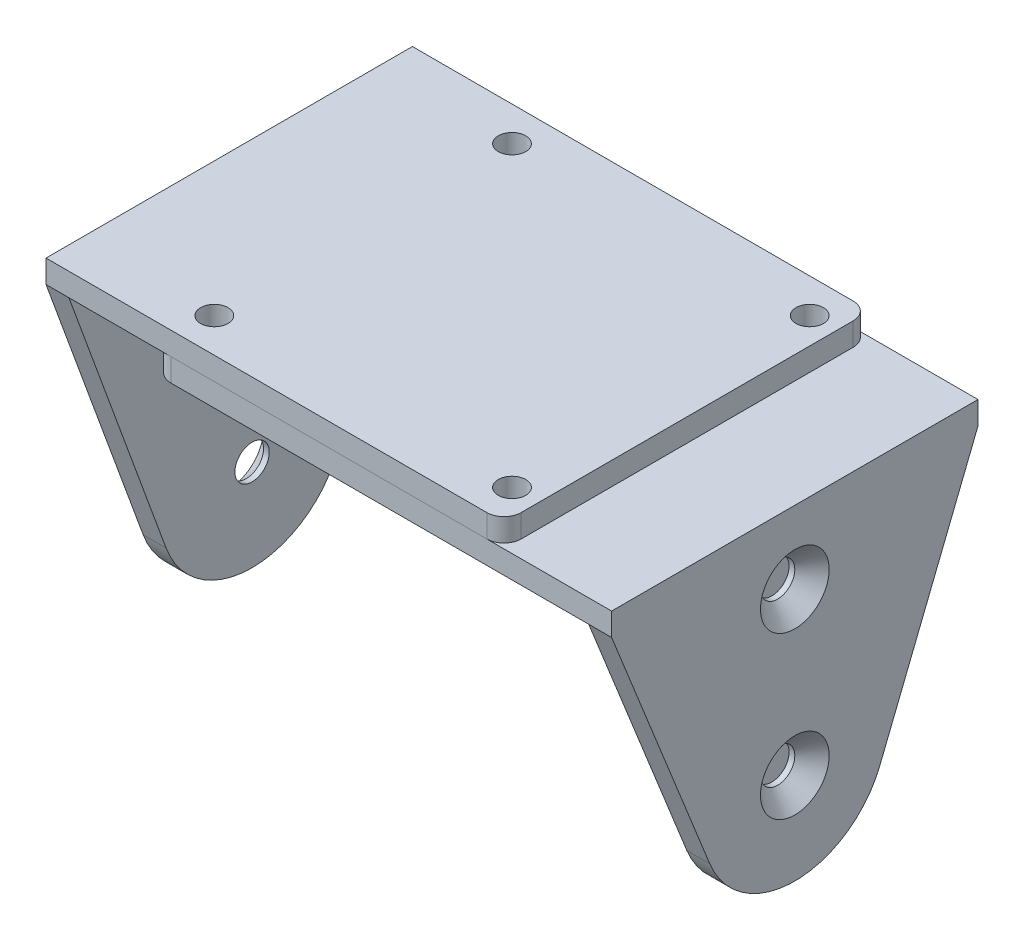
SolidWorks part; units mm, degrees
ref_plane "Спереди" through (0, 0, 0) normal (0, 0, 1) x (1, 0, 0)
ref_plane "Сверху" through (0, 0, 0) normal (0, 1, 0) x (1, 0, 0)
ref_plane "Справа" through (0, 0, 0) normal (1, 0, 0) x (0, 0, -1)
sketch "Эскиз1" plane through (0, 0, 0) normal (0, 1, 0) x (1, 0, 0)
  line L0 (0, 39.0615) -> (0, -43.4509) construction
  line L1 (-31.8334, 0) -> (63.9703, 0) construction
  line L2 (0, 16) -> (40, 16)
  line L3 (0, 16) -> (0, -16)
  line L4 (0, -16) -> (40, -16)
  line L5 (40, 16) -> (40, -16)
  line L7 (37.7, -13) -> (11.7, -13) construction
  line L8 (37.7, -13) -> (37.7, 13) construction
  line L9 (37.7, 13) -> (11.7, 13) construction
  line L10 (11.7, -13) -> (11.7, 13) construction
  line L11 (37.7, -13) -> (11.7, 13) construction
  line L12 (37.7, 13) -> (11.7, -13) construction
  circle A0 centre (11.7, 13) radius 1.2
  circle A1 centre (37.7, 13) radius 1.2
  circle A2 centre (37.7, -13) radius 1.2
  circle A3 centre (11.7, -13) radius 1.2
  point P9 (24.7, 0)
  dimension "D6" = 2.4
  dimension "D1" = 32
  dimension "D2" = 40
  dimension "D3" = 11.7
  dimension "D4" = 26
  dimension "D5" = 26
  dimension "D7" = 2
  dimension "D8" = 2
extrude "уголок 1 - основание" add sketch "Эскиз1" along normal blind 2
sketch "Эскиз2" plane through (0, 0, 0) normal (0, 1, 0) x (1, 0, 0)
  line L0 (-7.9027, 0) -> (56.365, 0) construction
  line L1 (49.4, 26.5876) -> (49.4, -26.9307) construction
  line L4 (37.7, -13) -> (11.7, -13) construction
  line L5 (37.7, -13) -> (37.7, 13) construction
  line L6 (37.7, 13) -> (11.7, 13) construction
  line L7 (11.7, -13) -> (11.7, 13) construction
  line L8 (37.7, -13) -> (11.7, 13) construction
  line L9 (37.7, 13) -> (11.7, -13) construction
  line L10 (49.4, -16) -> (9.4, -16)
  line L11 (49.4, -16) -> (49.4, 16)
  line L12 (49.4, 16) -> (9.4, 16)
  line L13 (9.4, -16) -> (9.4, 16)
  line L14 (49.4, -16) -> (9.4, 16) construction
  line L15 (49.4, 16) -> (9.4, -16) construction
  circle A0 centre (11.7, 13) radius 1.2
  circle A1 centre (37.7, 13) radius 1.2
  circle A2 centre (37.7, -13) radius 1.2
  circle A3 centre (11.7, -13) radius 1.2
  point P7 (24.7, 0)
  point P14 (29.4, 0)
  dimension "D3" = 2.4
  dimension "D4" = 2
  dimension "D1" = 11.7
  dimension "D2" = 26
  dimension "D6" = 40
  dimension "D7" = 32
  dimension "D5" = 2
extrude "уголок 2 - основание" add sketch "Эскиз2" against normal blind 2 separate body
sketch "Эскиз3" plane through (0, 0, 0) normal (-1, 0, 0) x (0, 0, 1)
  line L0 (0, 8.4121) -> (0, -39.4718) construction
  line L1 (-16, 0) -> (-7.5122, -23.179)
  line L2 (16, 0) -> (7.5122, -23.179)
  line L3 (-16, 0) -> (16, 0)
  line L5 (-16, 2) -> (16, 2) construction
  arc A0 (-7.5122, -23.179) -> (7.5122, -23.179) centre (0, -20.4282) ccw
  circle A1 centre (0, -20.4282) radius 1.5
  point P12 (-28.1067, -11.0581)
  dimension "D1" = 8
  dimension "D2" = 3
  dimension "D3" = 22.4282
extrude "уголок 1 - бок" add sketch "Эскиз3" against normal blind 2
sketch "Эскиз4" plane through (49.4, 0, 0) normal (1, 0, 0) x (0, 0, -1)
  line L0 (0, 14.6414) -> (0, -44.7384) construction
  line L1 (16, -2) -> (7.4263, -23.4031)
  line L2 (-16, -2) -> (-7.4263, -23.4031)
  line L3 (-16, 0) -> (16, 0) construction
  line L4 (-16, -2) -> (16, -2)
  circle A0 centre (0, -20.4282) radius 1.5
  arc A1 (-7.4263, -23.4031) -> (7.4263, -23.4031) centre (0, -20.4282) ccw
  circle A2 centre (0, -6.35) radius 1.5
  dimension "D1" = 3
  dimension "D2" = 8
  dimension "D3" = 3
  dimension "D4" = 6.35
extrude "уголок 2 - бок" add sketch "Эскиз4" against normal blind 2
fillet "Скругление1" radius 1.5 2 edges at (9.4, -1, 16) (9.4, -1, -16)
fillet "Скругление2" radius 1.5 2 edges at (40, 1, -16) (40, 1, 16)
chamfer "Фаска1" distance 1.5 angle 45 2 edges at (49.4, -20.4282, -1.5) (49.4, -6.35, -1.5)
chamfer "Фаска2" distance 1.5 angle 45 1 edges at (0, -20.4282, 1.5)
sketch "Эскиз5" plane through (47.4, 0, 0) normal (-1, 0, 0) x (0, 0, 1)
  line L0 (0, -35.2177) -> (0, 5.9258) construction
  line L1 (4.9, -2.3782) -> (-4.9, -2.3782)
  line L2 (4.9, -2.3782) -> (6.4256, -19.8677)
  line L3 (-4.9, -2.3782) -> (-6.4256, -19.8677)
  arc A0 (-6.4256, -19.8677) -> (6.4256, -19.8677) centre (0, -20.4282) ccw
  point P8 (0, -26.8782)
  point P9 (0, -2.3782)
  dimension "D1" = 6.45
  dimension "D2" = 24.5
  dimension "D3" = 9.8
extrude "Бобышка-Вытянуть5" add sketch "Эскиз5" along normal blind 2.6 separate body
sketch "Эскиз6" plane through (44.8, 0, 0) normal (-1, 0, 0) x (0, 0, 1)
  circle A0 centre (0, -20.4282) radius 4.85
  dimension "D1" = 9.7
extrude "Бобышка-Вытянуть6" add sketch "Эскиз6" along normal blind 1.6 separate body
chamfer "Фаска3" distance 1.4 angle 45 1 edges at (43.2, -20.4282, 4.85)
ref_axis "Ось кручения" through (56.3089, -20.4282, 0) along (-1, 0, 0)
ref_axis "Ось2" through (37.7, 4.7326, -13) along (0, -1, 0)
ref_axis "Ось3" through (37.7, 4.5925, 13) along (0, -1, 0)
ref_axis "Ось4" through (11.7, 4.6626, 13) along (0, -1, 0)
ref_axis "Ось5" through (11.7, 4.6626, -13) along (0, -1, 0)
